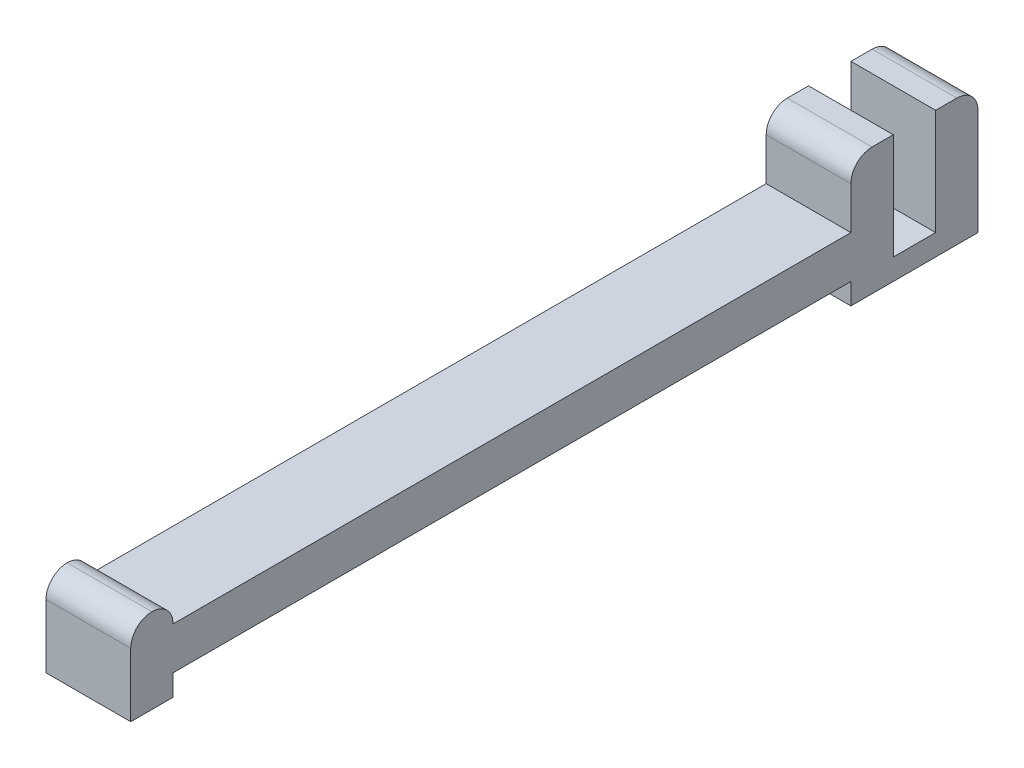
SolidWorks part; units mm, degrees
ref_plane "Front Plane" through (0, 0, 0) normal (0, 0, 1) x (1, 0, 0)
ref_plane "Top Plane" through (0, 0, 0) normal (0, 1, 0) x (1, 0, 0)
ref_plane "Right Plane" through (0, 0, 0) normal (1, 0, 0) x (0, 0, -1)
sketch "Sketch2" plane through (0, 0, 0) normal (1, 0, 0) x (0, 0, -1)
  line L0 (-160, 10) -> (-160, 20)
  line L1 (160, -10) -> (-160, -10)
  line L3 (160, 10) -> (-160, 10)
  line L5 (160, -10) -> (-160, 10) construction
  line L6 (160, 10) -> (-160, -10) construction
  line L7 (-160, 20) -> (-180, 20)
  line L8 (-180, 20) -> (-180, -20)
  line L9 (-180, -20) -> (-160, -20)
  line L10 (-160, -20) -> (-160, -10)
  line L11 (160, 10) -> (160, 40)
  line L12 (160, 40) -> (180, 40)
  line L13 (180, 40) -> (180, -10)
  line L14 (180, -20) -> (160, -20)
  line L15 (160, -20) -> (160, -10)
  line L16 (180, -20) -> (220, -20)
  line L17 (220, -20) -> (220, 40)
  line L18 (180, -10) -> (200, -10)
  line L19 (200, -10) -> (200, 40)
  line L20 (200, 40) -> (220, 40)
  point P0 (0, 0)
  point P18 (-170, -20)
  dimension "D1" = 20
  dimension "D2" = 60
  dimension "D3" = 40
  dimension "D4" = 10
  dimension "D5" = 10
  dimension "D6" = 20
  dimension "D7" = 20
  dimension "D8" = 360
  dimension "D9" = 60
  dimension "D10" = 20
  dimension "D11" = 10
  dimension "D12" = 320
  dimension "D13" = 20
  dimension "D14" = 60
  dimension "D15" = 60
  dimension "D16" = 180
  dimension "D17" = 20
extrude "Boss-Extrude1" add sketch "Sketch2" along normal blind 40
fillet "Fillet1" radius 10 2 edges at (20, 20, 180) (20, 20, 160)
fillet "Fillet2" radius 10 2 edges at (20, 40, -160) (20, 40, -220)
